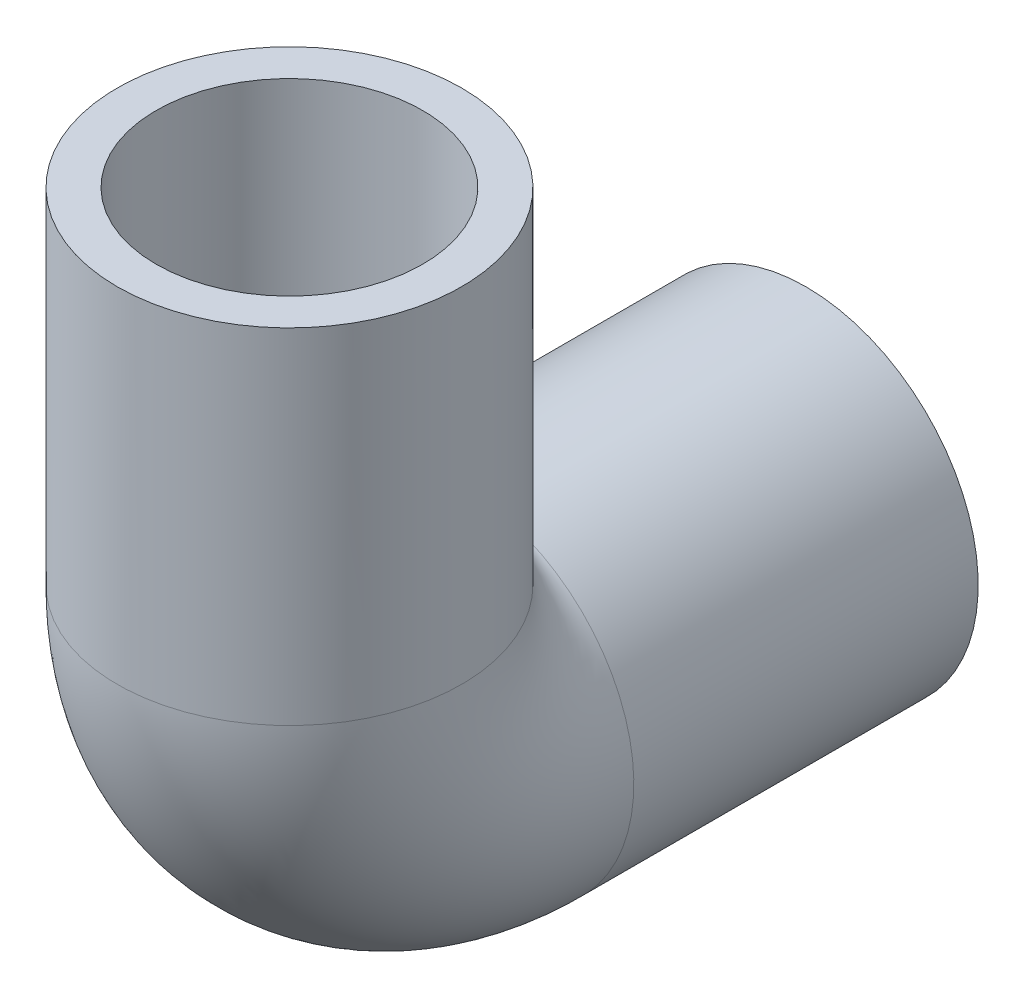
SolidWorks part; units mm, degrees
ref_plane "Front Plane" through (0, 0, 0) normal (0, 0, 1) x (1, 0, 0)
ref_plane "Top Plane" through (0, 0, 0) normal (0, 1, 0) x (1, 0, 0)
ref_plane "Right Plane" through (0, 0, 0) normal (1, 0, 0) x (0, 0, -1)
sketch "Sketch2" plane through (0, 0, 0) normal (0, 1, 0) x (1, 0, 0)
  circle A0 centre (0, 0) radius 12.7
  circle A1 centre (0, 0) radius 9.8298
  dimension "D1" = 25.4
  dimension "D2" = 2.8702
sketch "Sketch3" plane through (0, 0, 0) normal (1, 0, 0) x (0, 0, -1)
  line L0 (0, 0) -> (0, -25.4)
  line L1 (12.7, -38.1) -> (38.1, -38.1)
  arc A0 (0, -25.4) -> (12.7, -38.1) centre (12.7, -25.4) ccw
  dimension "D3" = 25.4
sweep "Sweep1" add profiles "Sketch2" path "Sketch3"
